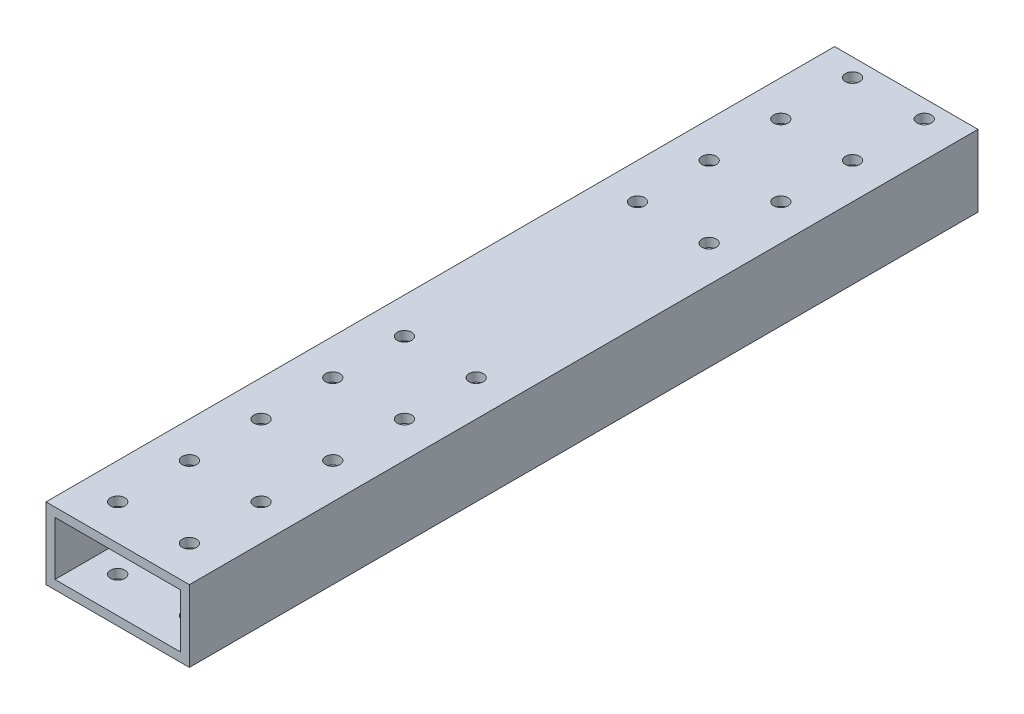
SolidWorks part; units mm, degrees
ref_plane "Front Plane" through (0, 0, 0) normal (0, 0, 1) x (1, 0, 0)
ref_plane "Top Plane" through (0, 0, 0) normal (0, 1, 0) x (1, 0, 0)
ref_plane "Right Plane" through (0, 0, 0) normal (1, 0, 0) x (0, 0, -1)
sketch "Sketch1" plane through (0, 0, 0) normal (0, 0, 1) x (1, 0, 0)
  line L1 (-25.4, -12.7) -> (25.4, -12.7)
  line L2 (-25.4, -12.7) -> (-25.4, 12.7)
  line L3 (-25.4, 12.7) -> (25.4, 12.7)
  line L4 (25.4, -12.7) -> (25.4, 12.7)
  line L5 (-25.4, -12.7) -> (25.4, 12.7) construction
  line L6 (-25.4, 12.7) -> (25.4, -12.7) construction
  line L7 (-22.225, -9.525) -> (22.225, -9.525)
  line L8 (-22.225, -9.525) -> (-22.225, 9.525)
  line L9 (-22.225, 9.525) -> (22.225, 9.525)
  line L10 (22.225, -9.525) -> (22.225, 9.525)
  line L11 (-22.225, -9.525) -> (22.225, 9.525) construction
  line L12 (-22.225, 9.525) -> (22.225, -9.525) construction
  point P0 (0, 0)
  point P6 (0, 0)
  dimension "D1" = 50.8
  dimension "D2" = 25.4
  dimension "D3" = 44.45
  dimension "D4" = 19.05
extrude "Boss-Extrude1" add sketch "Sketch1" along normal blind 279.4
sketch "Sketch2" plane through (0, 12.7, 0) normal (0, 1, 0) x (1, 0, 0)
  line L0 (-25.4, -139.7) -> (25.4, -139.7) construction
  line L1 (-25.4, -279.4) -> (-25.4, 0) construction
  line L2 (25.4, -279.4) -> (25.4, 0) construction
  line L3 (25.4, 0) -> (-25.4, 0) construction
  line L5 (25.4, -279.4) -> (-25.4, -279.4) construction
  circle A0 centre (-12.7, -6.35) radius 2.54
  circle A12 centre (-12.7, -266.7) radius 2.54
  circle A13 centre (12.7, -266.7) radius 2.54
  circle A14 centre (12.7, -241.3) radius 2.54
  circle A15 centre (12.7, -215.9) radius 2.54
  circle A16 centre (12.7, -190.5) radius 2.54
  circle A17 centre (12.7, -165.1) radius 2.54
  circle A18 centre (-12.7, -241.3) radius 2.54
  circle A19 centre (-12.7, -215.9) radius 2.54
  circle A20 centre (-12.7, -190.5) radius 2.54
  circle A21 centre (-12.7, -165.1) radius 2.54
  circle A22 centre (12.7, -6.35) radius 2.54
  circle A23 centre (12.7, -31.75) radius 2.54
  circle A24 centre (12.7, -57.15) radius 2.54
  circle A25 centre (-12.7, -31.75) radius 2.54
  circle A26 centre (-12.7, -57.15) radius 2.54
  circle A27 centre (-12.7, -82.55) radius 2.54
  circle A28 centre (12.7, -82.55) radius 2.54
  dimension "D1" = 6.35
  dimension "D5" = 12.7
  dimension "D2" = 12.7
  dimension "D6" = 12.7
  dimension "D7" = 2
  dimension "D8" = 5
  dimension "D3" = 2
  dimension "D4" = 4
extrude "Cut-Extrude1" cut sketch "Sketch2" against normal up to surface (25.4 mm away) up to face at (0, -12.7, 139.7)
